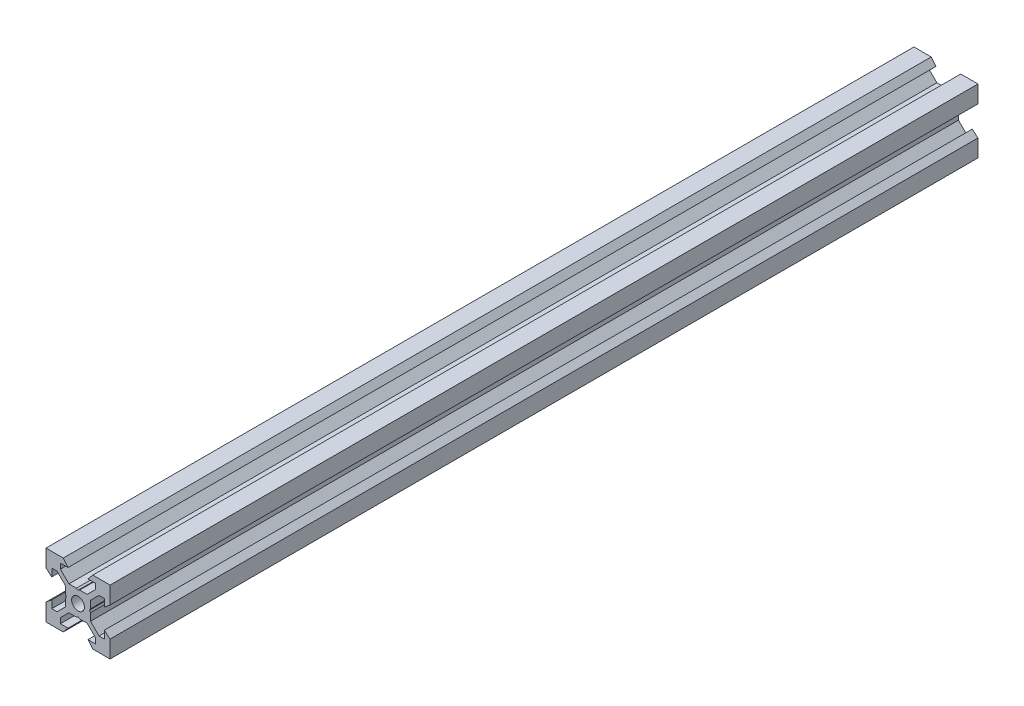
SolidWorks part; units mm, degrees
ref_plane "Front Plane" through (0, 0, 0) normal (0, 0, 1) x (1, 0, 0)
ref_plane "Top Plane" through (0, 0, 0) normal (0, 1, 0) x (1, 0, 0)
ref_plane "Right Plane" through (0, 0, 0) normal (1, 0, 0) x (0, 0, -1)
sketch "Sketch1" plane through (0, 0, 0) normal (0, 0, 1) x (1, 0, 0)
  line L0 (10, 10) -> (4.6104, 10) construction
  line L1 (10, 10) -> (10, 4.6104) construction
  line L2 (10, -10) -> (10, -4.6104) construction
  line L3 (10, -10) -> (4.6104, -10) construction
  line L4 (10, 10) -> (10, 4.6104)
  line L5 (6.5607, 5.5) -> (8.2, 5.5)
  line L6 (5.5, 8.2) -> (5.5, 6.5607)
  line L7 (10, 10) -> (4.6104, 10)
  line L8 (10, 10) -> (10, 4.6104)
  line L9 (6.5607, 5.5) -> (3.9, 2.8393)
  line L10 (5.5, 6.5607) -> (2.8393, 3.9)
  line L11 (10, 4.6104) -> (8.2, 3.1)
  line L12 (4.6104, 10) -> (3.1, 8.2)
  line L13 (8.2, 3.1) -> (8.2, 5.5)
  line L14 (3.1, 8.2) -> (5.5, 8.2)
  line L15 (-6.5607, 5.5) -> (-8.2, 5.5)
  line L16 (6.5607, -5.5) -> (8.2, -5.5)
  line L17 (3.1, -8.2) -> (5.5, -8.2)
  line L18 (8.2, -3.1) -> (8.2, -5.5)
  line L19 (4.6104, -10) -> (3.1, -8.2)
  line L20 (10, -4.6104) -> (8.2, -3.1)
  line L21 (0.5196, -3.9) -> (0, -3.6)
  line L22 (0.5196, 3.9) -> (0, 3.6)
  line L23 (3.6, 0) -> (3.9, -0.5196)
  line L24 (3.9, 0.5196) -> (3.6, 0)
  line L25 (3.9, 0.5196) -> (3.9, 2.8393)
  line L26 (2.8393, 3.9) -> (0.5196, 3.9)
  line L27 (3.9, -2.8393) -> (3.9, -0.5196)
  line L28 (2.8393, -3.9) -> (0.5196, -3.9)
  line L29 (5.5, -6.5607) -> (2.8393, -3.9)
  line L30 (6.5607, -5.5) -> (3.9, -2.8393)
  line L31 (10, -10) -> (10, -4.6104)
  line L32 (10, -10) -> (4.6104, -10)
  line L33 (5.5, -8.2) -> (5.5, -6.5607)
  line L34 (-6.5607, -5.5) -> (-8.2, -5.5)
  line L35 (10, -10) -> (10, -4.6104)
  line L36 (0, 0) -> (0, 8.2) construction
  line L37 (-10, -10) -> (-4.6104, -10) construction
  line L38 (-10, -10) -> (-10, -4.6104) construction
  line L39 (-10, 10) -> (-10, 4.6104) construction
  line L40 (-10, 10) -> (-4.6104, 10) construction
  line L41 (-10, -10) -> (-10, -4.6104)
  line L43 (-5.5, -8.2) -> (-5.5, -6.5607)
  line L44 (-10, -10) -> (-4.6104, -10)
  line L45 (-10, -10) -> (-10, -4.6104)
  line L46 (-6.5607, -5.5) -> (-3.9, -2.8393)
  line L47 (-5.5, -6.5607) -> (-2.8393, -3.9)
  line L48 (-2.8393, -3.9) -> (-0.5196, -3.9)
  line L49 (-3.9, -2.8393) -> (-3.9, -0.5196)
  line L50 (-2.8393, 3.9) -> (-0.5196, 3.9)
  line L51 (-3.9, 0.5196) -> (-3.9, 2.8393)
  line L52 (-3.9, 0.5196) -> (-3.6, 0)
  line L53 (-3.6, 0) -> (-3.9, -0.5196)
  line L54 (-0.5196, 3.9) -> (0, 3.6)
  line L55 (-0.5196, -3.9) -> (0, -3.6)
  line L56 (-10, -4.6104) -> (-8.2, -3.1)
  line L57 (-4.6104, -10) -> (-3.1, -8.2)
  line L58 (-8.2, -3.1) -> (-8.2, -5.5)
  line L59 (-3.1, -8.2) -> (-5.5, -8.2)
  line L60 (-10, -10) -> (10, -10) construction
  line L61 (-10, -10) -> (-10, 10) construction
  line L62 (-3.1, 8.2) -> (-5.5, 8.2)
  line L63 (-8.2, 3.1) -> (-8.2, 5.5)
  line L64 (-4.6104, 10) -> (-3.1, 8.2)
  line L65 (-10, 4.6104) -> (-8.2, 3.1)
  line L66 (-5.5, 6.5607) -> (-2.8393, 3.9)
  line L67 (-6.5607, 5.5) -> (-3.9, 2.8393)
  line L68 (-10, 10) -> (-10, 4.6104)
  line L69 (-10, 10) -> (-4.6104, 10)
  line L70 (-5.5, 8.2) -> (-5.5, 6.5607)
  line L71 (-10, 10) -> (10, 10) construction
  line L72 (-10, 10) -> (-10, 4.6104)
  line L73 (10, -10) -> (10, 10) construction
  line L74 (-10, -10) -> (10, 10) construction
  line L75 (-10, 10) -> (10, -10) construction
  circle A0 centre (0, 0) radius 2
  dimension "D7" = 4
  dimension "D1" = 20
  dimension "D2" = 5.3896
  dimension "D3" = 4.5
  dimension "D4" = 50
  dimension "D5" = 1.8
  dimension "D6" = 1.5104
  dimension "D8" = 5.5
  dimension "D9" = 120
  dimension "D10" = 0.3
  dimension "D11" = 2.3197
  dimension "D12" = 7.8
  dimension "D13" = 7.8
  dimension "D14" = 1.5
  dimension "D15" = 2.6607
extrude "Boss-Extrude1" add sketch "Sketch1" along normal mid plane 271 contours L70 L62 L64 L69 L68 L65 L63 L15 L67 L51 L52 L53 L49 L46 L34 L58 L56 L41 L44 L57 L59 L43 L47 L48 L55 L21 L28 L29 L33 L17 L19 L32 L31 L20 L18 L16 L30 L27 L23 L24 L25 L9 L5 L13 L11 L4 L7 L12 L14 L6 L10 region at (9.7172, 7.3052, 0)
